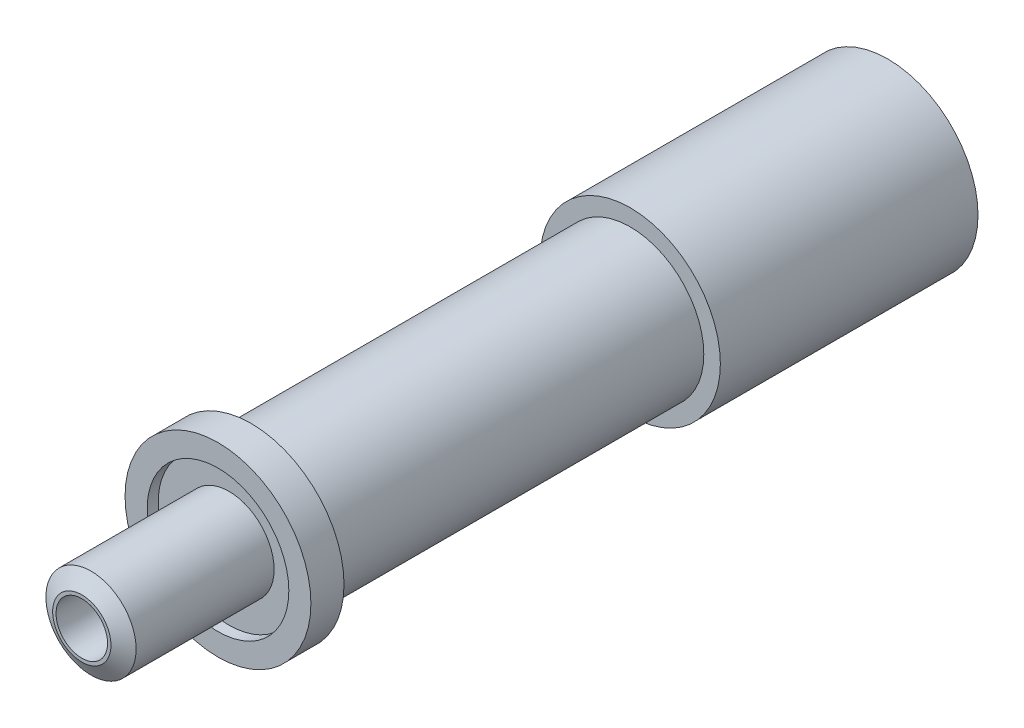
SolidWorks part; units mm, degrees
ref_plane "Front Plane" through (0, 0, 0) normal (0, 0, 1) x (1, 0, 0)
ref_plane "Top Plane" through (0, 0, 0) normal (0, 1, 0) x (1, 0, 0)
ref_plane "Right Plane" through (0, 0, 0) normal (1, 0, 0) x (0, 0, -1)
sketch "Sketch1" plane through (0, 0, 0) normal (0, 1, 0) x (1, 0, 0)
  line L0 (0, 24.784) -> (0, 10.1)
  line L1 (0, 10.1) -> (0.6, 10.1)
  line L2 (0.6, 10.1) -> (0.7, 3.1)
  line L3 (0.7, 3.1) -> (0.792, 3.1)
  line L4 (0.792, 3.1) -> (1.225, 3.35)
  line L5 (1.225, 3.35) -> (1.225, 7.1)
  line L6 (1.225, 7.1) -> (1.925, 7.1)
  line L7 (1.925, 7.1) -> (1.925, 6.8)
  line L8 (1.925, 6.8) -> (2.525, 6.8)
  line L9 (2.525, 6.8) -> (2.525, 7.7)
  line L10 (2.525, 7.7) -> (2, 7.7)
  line L11 (2, 7.7) -> (2, 18)
  line L12 (2, 18) -> (2.45, 18)
  line L13 (2.45, 18) -> (2.45, 24)
  line L14 (2.45, 24) -> (4.2, 24)
  line L15 (4.2, 24) -> (4.2, 18)
  line L16 (4.2, 18) -> (5, 18)
  line L17 (5, 18) -> (5, 25)
  line L18 (0, 25.5) -> (0, 3.1) construction
  arc A0 (4.3448, 25.4753) -> (0, 24.784) centre (0, 38.784) cw
  arc A1 (5, 25) -> (4.3448, 25.4753) centre (4.5, 25) ccw
revolve "Revolve1" add sketch "Sketch1" angle 360 about L18 reverse direction yes
sketch "Sketch2" plane through (0, 0, -18) normal (0, 0, 1) x (1, 0, 0)
  circle A0 centre (0, 0) radius 2.45
  circle A1 centre (0, 0) radius 5
  dimension "D1" = 4.9
extrude "Cut-Extrude1" cut sketch "Sketch2" against normal blind 10
